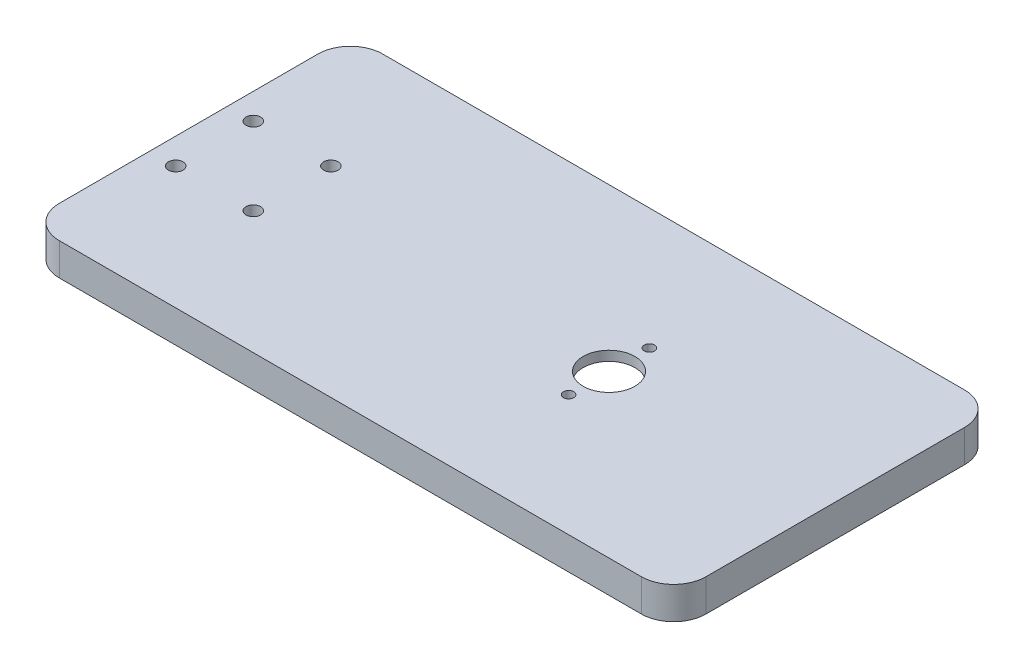
SolidWorks part; units mm, degrees
ref_plane "正面" through (0, 0, 0) normal (0, 0, 1) x (1, 0, 0)
ref_plane "平面" through (0, 0, 0) normal (0, 1, 0) x (1, 0, 0)
ref_plane "右側面" through (0, 0, 0) normal (1, 0, 0) x (0, 0, -1)
sketch "ｽｹｯﾁ1" plane through (0, 0, 0) normal (0, 1, 0) x (1, 0, 0)
  line L1 (-100, -50) -> (100, -50)
  line L2 (-100, -50) -> (-100, 50)
  line L3 (-100, 50) -> (100, 50)
  line L4 (100, -50) -> (100, 50)
  line L5 (-100, -50) -> (100, 50) construction
  line L6 (-100, 50) -> (100, -50) construction
  point P0 (0, 0)
  dimension "D1" = 200
  dimension "D2" = 100
extrude "ﾎﾞｽ - 押し出し1" add sketch "ｽｹｯﾁ1" along normal blind 10
sketch "ｽｹｯﾁ2" plane through (0, 10, 0) normal (0, 1, 0) x (1, 0, 0)
  line L0 (30, 0) -> (-80, 0) construction
  line L1 (-100, 50) -> (-100, -50) construction
  circle A0 centre (-92, 12) radius 2.25
  circle A1 centre (-68, 12) radius 2.25
  circle A2 centre (-92, -12) radius 2.25
  circle A3 centre (-68, -12) radius 2.25
  circle A4 centre (30, 0) radius 8
  circle A5 centre (30, 12.5) radius 1.6
  circle A6 centre (30, -12.5) radius 1.6
  dimension "D3" = 4.5
  dimension "D8" = 16
  dimension "D9" = 3.2
  dimension "D1" = 110
  dimension "D2" = 20
  dimension "D4" = 24
  dimension "D5" = 24
  dimension "D6" = 12
  dimension "D7" = 12
  dimension "D10" = 25
  dimension "D11" = 12.5
extrude "ｶｯﾄ - 押し出し1" cut sketch "ｽｹｯﾁ2" against normal through all
sketch "ｽｹｯﾁ3" plane through (0, 0, 0) normal (0, -1, 0) x (1, 0, 0)
  circle A0 centre (30, 0) radius 19
  dimension "D1" = 38
extrude "ｶｯﾄ - 押し出し2" cut sketch "ｽｹｯﾁ3" against normal offset from surface (7 mm away) 3 up to face at (30, 10, -10.9)
sketch "ｽｹｯﾁ4" plane through (0, 0, 0) normal (0, -1, 0) x (1, 0, 0)
  line L21 (-100, 50) -> (100, 50) construction
  line L22 (-100, -50) -> (-100, 50) construction
  line L23 (100, 50) -> (100, -50) construction
  line L24 (100, -50) -> (-100, -50) construction
  circle A0 centre (-85, 35) radius 5.1
  circle A1 centre (-85, -35) radius 5.1
  circle A2 centre (85, -35) radius 5.1
  circle A3 centre (85, 35) radius 5.1
  point P8 (0, 0)
  point P9 (0, 0)
  point P10 (0, 0)
  point P11 (0, 0)
  point P12 (-84.6762, 35.513)
  dimension "D1" = 10.2
  dimension "D2" = 15
  dimension "D3" = 15
  dimension "D4" = 15
  dimension "D5" = 15
fillet "ﾌｨﾚｯﾄ1" radius 10 4 edges at (100, 5, -50) (-100, 5, -50) (100, 5, 50) (-100, 5, 50)
extrude "ｶｯﾄ - 押し出し4" cut sketch "ｽｹｯﾁ4" against normal blind 5
